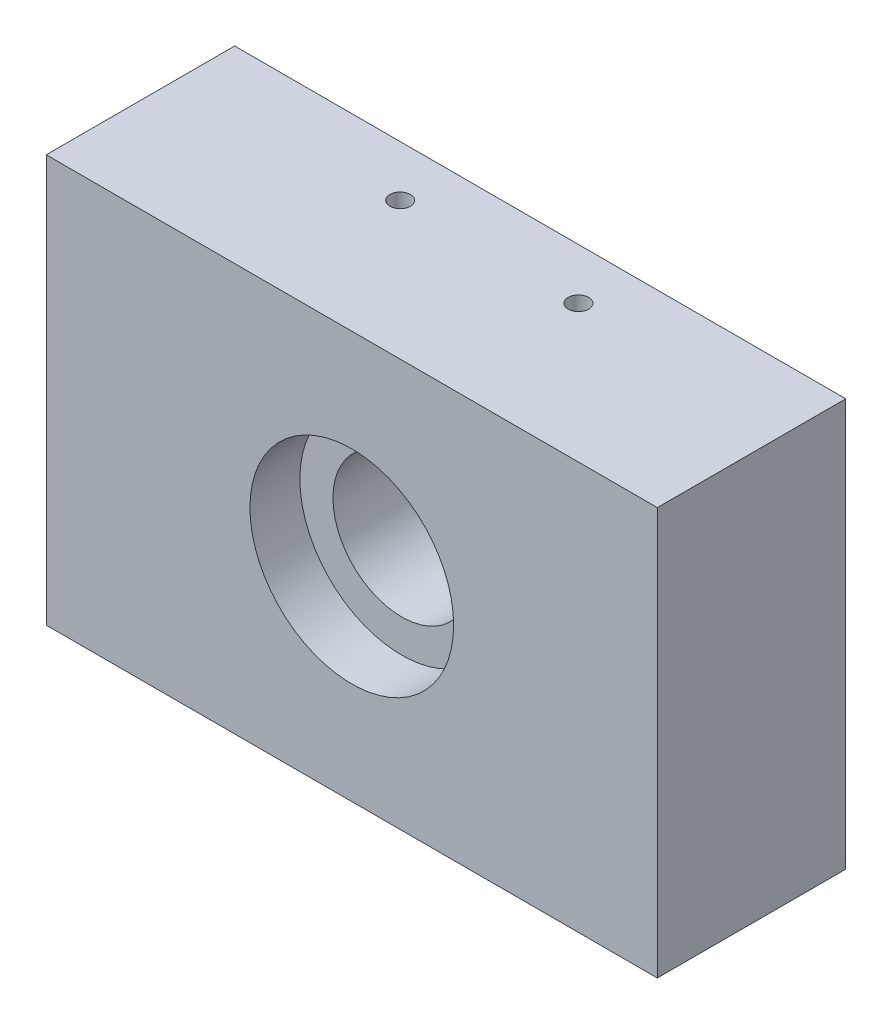
SolidWorks part; units mm, degrees
material "1060 Alloy"
ref_plane "Front Plane" through (0, 0, 0) normal (0, 0, 1) x (1, 0, 0)
ref_plane "Top Plane" through (0, 0, 0) normal (0, 1, 0) x (1, 0, 0)
ref_plane "Right Plane" through (0, 0, 0) normal (1, 0, 0) x (0, 0, -1)
sketch "Sketch1" plane through (0, 0, 0) normal (0, 0, 1) x (1, 0, 0)
  line L1 (0, 0) -> (152.4, 0)
  line L2 (0, 0) -> (0, 101.6)
  line L3 (0, 101.6) -> (152.4, 101.6)
  line L4 (152.4, 0) -> (152.4, 101.6)
  dimension "D1" = 152.4
  dimension "D2" = 101.6
extrude "Boss-Extrude1" add sketch "Sketch1" along normal blind 46.99
sketch "Sketch2" plane through (0, 0, 0) normal (0, 0, -1) x (-1, 0, 0)
  line L0 (0, 50.8) -> (-152.4, 50.8) construction
  line L1 (0, 101.6) -> (0, 0) construction
  line L2 (-152.4, 0) -> (-152.4, 101.6) construction
  line L4 (-152.4, 101.6) -> (0, 101.6) construction
  line L5 (-76.2, 101.6) -> (-76.2, 0) construction
  line L6 (0, 0) -> (-152.4, 0) construction
  circle A0 centre (-76.2, 50.8) radius 25.4
  circle A1 centre (-76.2, 50.8) radius 17.145
  dimension "D1" = 50.8
  dimension "D2" = 34.29
extrude "Cut-Extrude1" cut sketch "Sketch2" against normal through all contours A1
extrude "Cut-Extrude3" cut sketch "Sketch2<2>" against normal blind 12.446
sketch "Sketch2<2>" plane through (0, 0, 0) normal (0, 0, -1) x (-1, 0, 0) same geometry as "Sketch2"
ref_plane "Plane2" through (0, 0, 23.495) normal (0, 0, -1) x (-1, 0, 0)
mirror "Mirror2" about plane through (0, 0, 23.495) normal (0, 0, -1) of "Cut-Extrude3"
hole_wizard "Tap Drill for 1/2-13 Tap1" positions "Sketch4" profile "Sketch5" hole size "1/2-13" standard "ANSI Inch"
sketch "Sketch4" plane through (0, 0, 0) normal (0, -1, 0) x (-1, 0, 0)
  line L0 (55.88, -23.495) -> (-55.88, -23.495) construction
  line L2 (-76.2, -46.99) -> (-76.2, 0) construction
  line L3 (0, -46.99) -> (-152.4, -46.99) construction
  line L4 (0, 0) -> (-152.4, 0) construction
  point P0 (-68.0517, -23.495)
  point P4 (-29.9517, -23.495)
  dimension "D1" = 46.2483
  dimension "D2" = 38.1
sketch "Sketch5" plane through (68.0517, 0, 23.495) normal (1, 0, 0) x (0, 0, -1)
  line L0 (0, 0) -> (0, 22.2695)
  line L1 (0, 22.2695) -> (5.3581, 19.05)
  line L2 (5.3581, 19.05) -> (5.3581, 0)
  line L5 (5.3581, 0) -> (0, 0)
  line L10 (0, 22.2695) -> (-5.3581, 19.05) construction
  line L11 (0, -6.35) -> (0, 107.95) construction
  dimension "Hole Dia." = 10.7163
  dimension "Hole Depth" = 19.05
  dimension "Drill Angle" = 118
hole_wizard "Tap Drill for 1/4-20 Tap1" positions "Sketch7" profile "Sketch8" hole size "1/4-20" standard "ANSI Inch"
sketch "Sketch7" plane through (50.8, 101.6, 0) normal (0, -1, 0) x (0, 0, -1)
  line L3 (0, 101.6) -> (0, -50.8) construction
  line L4 (-46.99, -50.8) -> (0, -50.8) construction
  point P0 (-12.7, 47.625)
  point P2 (-12.7, 3.175)
  dimension "D1" = 12.7
  dimension "D2" = 12.7
  dimension "D3" = 44.45
  dimension "D4" = 53.975
sketch "Sketch8" plane through (98.425, 101.6, 12.7) normal (1, 0, 0) x (0, 0, 1)
  line L0 (0, 0) -> (0, 15.24)
  line L1 (0, 15.24) -> (2.5527, 13.7062)
  line L2 (2.5527, 13.7062) -> (2.5527, 0)
  line L5 (2.5527, 0) -> (0, 0)
  line L10 (0, 15.24) -> (-2.5527, 13.7062) construction
  line L11 (0, -6.35) -> (0, 107.95) construction
  dimension "Hole Dia." = 5.1054
  dimension "Hole Depth" = 15.24
  dimension "Drill Angle" = 118
equation "\"through_diamiter\"= 1.35"
equation "\"D2@Sketch2\"= \"through_diamiter\""
equation "\"bearing depth\"= 0.5"
equation "\"hole spacing\"= 0.75"
equation "\"D1@Sketch4\" = \"hole spacing\"+\"center_distance\""
equation "\"center_distance\"= 1.07080043"
